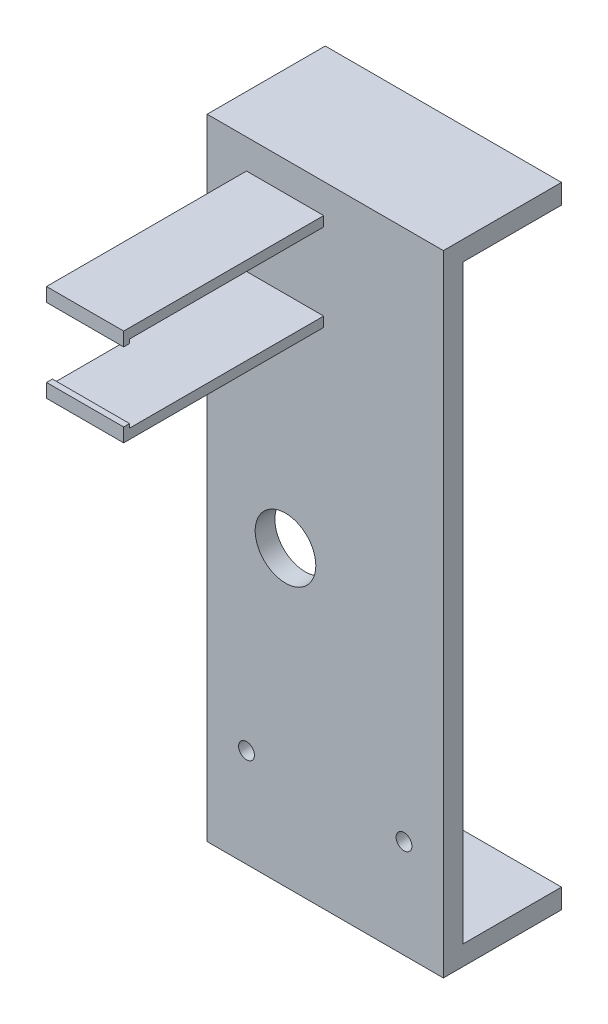
SolidWorks part; units mm, degrees
ref_plane "Front" through (0, 0, 0) normal (0, 0, 1) x (1, 0, 0)
ref_plane "Top" through (0, 0, 0) normal (0, 1, 0) x (1, 0, 0)
ref_plane "Right" through (0, 0, 0) normal (1, 0, 0) x (0, 0, -1)
sketch "Sketch1" plane through (0, 0, 0) normal (0, 0, 1) x (1, 0, 0)
  line L1 (-62.9053, 37.9943) -> (13.2947, 37.9943)
  line L2 (-62.9053, 37.9943) -> (-62.9053, -165.2057)
  line L3 (-62.9053, -165.2057) -> (13.2947, -165.2057)
  line L4 (13.2947, 37.9943) -> (13.2947, -165.2057)
  dimension "D1" = 76.2
  dimension "D2" = 203.2
extrude "Boss-Extrude1" add sketch "Sketch1" along normal blind 6.35
sketch "Sketch2" plane through (0, 0, 6.35) normal (0, 0, 1) x (1, 0, 0)
  line L0 (-50.2053, 0.4023) -> (-25.3133, 0.4023) construction
  line L1 (-25.3133, 25.2943) -> (-25.3133, 0.4023) construction
  line L2 (-50.2053, 25.2943) -> (-25.3133, 25.2943) construction
  line L3 (-50.2053, 25.2943) -> (-50.2053, 0.4023) construction
  line L4 (-50.2053, 0.4023) -> (-25.3133, 0.4023)
  line L5 (-25.3133, 25.2943) -> (-25.3133, 0.4023)
  line L6 (-50.2053, 25.2943) -> (-25.3133, 25.2943)
  line L7 (-50.2053, 25.2943) -> (-50.2053, 0.4023)
  line L9 (-25.3133, 0.4023) -> (-50.2053, 0.4023)
  line L10 (-25.3133, 0.4023) -> (-25.3133, -2.7727)
  line L11 (-25.3133, -2.7727) -> (-50.2053, -2.7727)
  line L12 (-50.2053, 0.4023) -> (-50.2053, -2.7727)
  line L13 (-25.3133, 25.2943) -> (-50.2053, 25.2943)
  line L14 (-25.3133, 25.2943) -> (-25.3133, 28.4693)
  line L15 (-25.3133, 28.4693) -> (-50.2053, 28.4693)
  line L16 (-50.2053, 25.2943) -> (-50.2053, 28.4693)
  circle A2 centre (-50.2053, -133.4557) radius 2.5527 construction
  circle A3 centre (0.5947, -133.4557) radius 2.5527 construction
  circle A4 centre (-50.2053, -133.4557) radius 2.5527
  circle A5 centre (0.5947, -133.4557) radius 2.5527
  circle A6 centre (-37.6323, -70.5907) radius 9.779 construction
  circle A7 centre (-37.6323, -70.5907) radius 9.779
  dimension "D1" = 3.175
  dimension "D2" = 3.175
extrude "Cut-Extrude1" cut sketch "Sketch2" against normal up to surface (6.35 mm away) contours A7 | A4 | A5 region at (-50.2053, -133.4557, 6.35) region at (0.5947, -133.4557, 6.35) region at (-37.6323, -70.5907, 6.35) up to face at (-24.8053, -63.6057, 0)
extrude "Boss-Extrude2" add sketch "Sketch2<3>" along normal up to surface (64.516 mm away) contours L16 L6 L14 L15 | L4 L12 L11 L10 region at (-37.7593, -1.1852, 6.35) region at (-37.7593, 26.8818, 6.35)
sketch "Sketch2<3>" plane through (0, 0, 6.35) normal (0, 0, 1) x (1, 0, 0) same geometry as "Sketch2"
sketch "Sketch3" plane through (0, 25.2943, 0) normal (0, -1, 0) x (1, 0, 0)
  line L4 (-50.2053, 68.961) -> (-25.3133, 68.961)
  line L5 (-50.2053, 70.866) -> (-50.2053, 68.961)
  line L6 (-25.3133, 70.866) -> (-50.2053, 70.866)
  line L7 (-25.3133, 68.961) -> (-25.3133, 70.866)
  line L8 (-50.2053, 68.961) -> (-25.3133, 68.961)
  line L9 (-50.2053, 70.866) -> (-50.2053, 68.961)
  line L10 (-25.3133, 70.866) -> (-50.2053, 70.866)
  line L11 (-25.3133, 68.961) -> (-25.3133, 70.866)
  dimension "D1" = 0
extrude "Boss-Extrude3" add sketch "Sketch3" along normal up to surface (1.27 mm away)
sketch "Sketch4" plane through (0, 0.4023, 0) normal (0, 1, 0) x (1, 0, 0)
  line L4 (-25.3133, -70.866) -> (-25.3133, -68.961)
  line L5 (-50.2053, -70.866) -> (-25.3133, -70.866)
  line L6 (-50.2053, -68.961) -> (-50.2053, -70.866)
  line L7 (-25.3133, -68.961) -> (-50.2053, -68.961)
  line L8 (-25.3133, -70.866) -> (-25.3133, -68.961)
  line L9 (-50.2053, -70.866) -> (-25.3133, -70.866)
  line L10 (-50.2053, -68.961) -> (-50.2053, -70.866)
  line L11 (-25.3133, -68.961) -> (-50.2053, -68.961)
  dimension "D1" = 0
extrude "Boss-Extrude4" add sketch "Sketch4" along normal up to surface (1.27 mm away)
sketch "Sketch5" plane through (0, 0, 0) normal (0, 0, -1) x (-1, 0, 0)
  line L0 (-13.2947, -165.2057) -> (-13.2947, 37.9943) construction
  line L1 (62.9053, 37.9943) -> (-13.2947, 37.9943)
  line L2 (62.9053, 37.9943) -> (62.9053, 31.6443)
  line L3 (62.9053, 31.6443) -> (-13.2947, 31.6443)
  line L4 (-13.2947, 37.9943) -> (-13.2947, 31.6443)
  line L6 (62.9053, -165.2057) -> (-13.2947, -165.2057)
  line L7 (62.9053, -165.2057) -> (62.9053, -158.8557)
  line L8 (62.9053, -158.8557) -> (-13.2947, -158.8557)
  line L9 (-13.2947, -165.2057) -> (-13.2947, -158.8557)
  dimension "D1" = 6.35
  dimension "D2" = 6.35
extrude "Boss-Extrude5" add sketch "Sketch5" along normal blind 31.75
